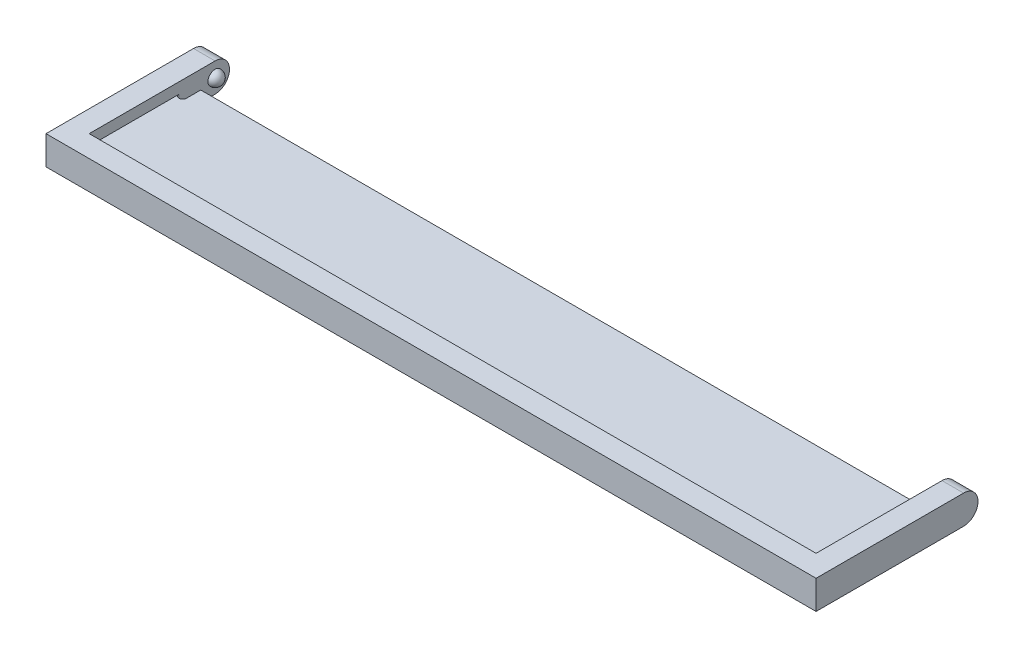
SolidWorks part; units mm, degrees
ref_plane "Alzado" through (0, 0, 0) normal (0, 0, 1) x (1, 0, 0)
ref_plane "Planta" through (0, 0, 0) normal (0, 1, 0) x (1, 0, 0)
ref_plane "Vista lateral" through (0, 0, 0) normal (1, 0, 0) x (0, 0, -1)
sketch "Croquis1" plane through (0, 0, 0) normal (0, 1, 0) x (1, 0, 0)
  line L1 (-64.6839, 30.0544) -> (36.3161, 30.0544)
  line L2 (-67.6839, 30.0544) -> (-67.6839, 10.5544)
  line L3 (-67.6839, 10.5544) -> (39.3161, 10.5544)
  line L4 (39.3161, 30.0544) -> (39.3161, 10.5544)
  line L6 (-67.6839, 30.0544) -> (-67.6839, 33.0544)
  line L7 (-67.6839, 33.0544) -> (-64.6839, 33.0544)
  line L8 (-64.6839, 30.0544) -> (-64.6839, 33.0544)
  line L10 (39.3161, 30.0544) -> (39.3161, 33.0544)
  line L11 (39.3161, 33.0544) -> (36.3161, 33.0544)
  line L12 (36.3161, 30.0544) -> (36.3161, 33.0544)
  dimension "D1" = 107
  dimension "D2" = 19.5
  dimension "D3" = 3
  dimension "D4" = 3
  dimension "D5" = 3
  dimension "D6" = 3
extrude "Saliente-Extruir1" add sketch "Croquis1" along normal blind 4
sketch "Croquis2" plane through (36.3161, 0, 0) normal (-1, 0, 0) x (0, 0, 1)
  line L0 (-33.0544, 4) -> (-33.0544, 0) construction
  line L1 (-33.0544, 4) -> (-30.0544, 4) construction
  line L2 (-32.0544, 2) -> (-30.0544, 2) construction
  line L3 (-32.0544, 2) -> (-30.0544, 2)
  arc A0 (-32.0544, 2) -> (-30.0544, 2) centre (-31.0544, 2) ccw
  dimension "D1" = 2
  dimension "D2" = 2
  dimension "D3" = 2
sketch "Croquis3" plane through (-64.6839, 0, 0) normal (1, 0, 0) x (0, 0, -1)
  line L0 (30.0544, 4) -> (33.0544, 4) construction
  line L1 (33.0544, 4) -> (33.0544, 0) construction
  line L2 (32.0544, 2) -> (30.0544, 2) construction
  line L3 (32.0544, 2) -> (30.0544, 2)
  arc A0 (30.0544, 2) -> (32.0544, 2) centre (31.0544, 2) ccw
  dimension "D1" = 2
  dimension "D2" = 2
  dimension "D3" = 2
sketch "Croquis4" plane through (0, 4, 0) normal (0, 1, 0) x (1, 0, 0)
  line L0 (36.3161, 30.0544) -> (36.3161, 26.0544)
  line L1 (35.3161, 30.0544) -> (35.3161, 26.0544)
  line L2 (36.3161, 30.0544) -> (-64.6839, 30.0544) construction
  line L3 (36.3161, 30.0544) -> (35.3161, 30.0544)
  line L4 (-64.6839, 30.0544) -> (-64.6839, 26.0544)
  line L5 (-63.6839, 30.0544) -> (-63.6839, 26.0544)
  line L6 (-64.6839, 30.0544) -> (-63.6839, 30.0544)
  line L8 (-63.6839, 30.0544) -> (35.3161, 30.0544)
  line L9 (-63.6839, 30.0544) -> (-63.6839, 28.0544)
  line L10 (-63.6839, 28.0544) -> (35.3161, 28.0544)
  line L11 (35.3161, 30.0544) -> (35.3161, 28.0544)
  arc A0 (35.3161, 26.0544) -> (36.3161, 26.0544) centre (35.8161, 26.0544) ccw
  arc A1 (-64.6839, 26.0544) -> (-63.6839, 26.0544) centre (-64.1839, 26.0544) ccw
  line M10 (36.3161, 30.0544) -> (-64.6839, 30.0544)
  dimension "D1" = 4
  dimension "D2" = 1
  dimension "D3" = 4
  dimension "D4" = 1
  dimension "D5" = 2
extrude "Cortar-Extruir1" cut sketch "Croquis4" against normal blind 10 contours L5 L10 L1 M10 | L1 A0 L0 M10 | L4 A1 L5 M10 region at (35.8161, 4, -27.8567) region at (-14.1839, 4, -29.0544) region at (-64.1839, 4, -27.8567)
fillet "Redondeo1" radius 2 4 edges at (-66.1839, 0, -33.0544) (-66.1839, 4, -33.0544) (37.8161, 0, -33.0544) (37.8161, 4, -33.0544)
revolve "Revolución1" add sketch "Croquis3" angle 360 about L2
revolve "Revolución2" add sketch "Croquis2" angle 360 about L2
sketch "Croquis5" plane through (0, 4, 0) normal (0, 1, 0) x (1, 0, 0)
  line L0 (-64.6839, 26.0544) -> (-64.6839, 31.0544) construction
  line L1 (-64.6839, 29.6257) -> (36.3161, 29.6257)
  line L2 (-64.6839, 29.6257) -> (-64.6839, 13.5544)
  line L3 (-64.6839, 13.5544) -> (36.3161, 13.5544)
  line L4 (36.3161, 29.6257) -> (36.3161, 13.5544)
  line L5 (-67.6839, 10.5544) -> (39.3161, 10.5544) construction
  line L6 (36.3161, 31.0544) -> (36.3161, 26.0544) construction
  dimension "D1" = 3
extrude "Cortar-Extruir2" cut sketch "Croquis5" against normal blind 1.5
